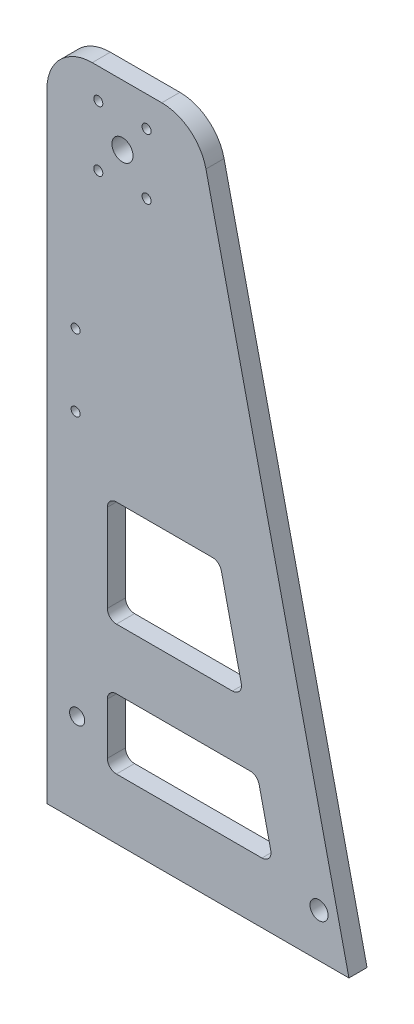
SolidWorks part; units mm, degrees
material "Policarbonato"
ref_plane "Plano frontal" through (0, 0, 0) normal (0, 0, 1) x (1, 0, 0)
ref_plane "Plano superior" through (0, 0, 0) normal (0, 1, 0) x (1, 0, 0)
ref_plane "Plano direito" through (0, 0, 0) normal (1, 0, 0) x (0, 0, -1)
sketch "Esboço1" plane through (0, 0, 0) normal (0, 0, 1) x (1, 0, 0)
  line L0 (0, 0) -> (0, 220)
  line L2 (100, 0) -> (0, 0)
  line L3 (0, 220) -> (50, 220)
  line L4 (50, 220) -> (100, 0)
  line L5 (10, 103) -> (10, 15) construction
  line L6 (25, 220) -> (25, 180) construction
  line L7 (10, 15) -> (75.8194, 15) construction
  line L8 (75.8194, 15) -> (55.8194, 103) construction
  line L9 (55.8194, 103) -> (10, 103) construction
  line L10 (20, 95) -> (20, 66)
  line L11 (23, 63) -> (61.4135, 63)
  line L12 (64.3389, 66.6649) -> (57.748, 95.6649)
  line L13 (54.8226, 98) -> (23, 98)
  line L14 (20, 40) -> (20, 23)
  line L15 (23, 20) -> (71.1862, 20)
  line L16 (74.1116, 23.6649) -> (70.248, 40.6649)
  line L17 (23, 43) -> (67.3226, 43)
  line L18 (17, 200) -> (33, 200) construction
  line L19 (17, 210) -> (33, 210) construction
  line L20 (17, 210) -> (17, 190) construction
  line L21 (17, 190) -> (33, 190) construction
  line L22 (33, 210) -> (33, 190) construction
  line L23 (17, 210) -> (33, 190) construction
  line L24 (17, 190) -> (33, 210) construction
  arc A8 (70.248, 40.6649) -> (67.3226, 43) centre (67.3226, 40) ccw
  arc A9 (71.1862, 20) -> (74.1116, 23.6649) centre (71.1862, 23) ccw
  arc A10 (20, 23) -> (23, 20) centre (23, 23) ccw
  arc A11 (20, 40) -> (23, 43) centre (23, 40) cw
  arc A12 (57.748, 95.6649) -> (54.8226, 98) centre (54.8226, 95) ccw
  arc A13 (61.4135, 63) -> (64.3389, 66.6649) centre (61.4135, 66) ccw
  arc A14 (20, 66) -> (23, 63) centre (23, 66) ccw
  arc A15 (20, 95) -> (23, 98) centre (23, 95) cw
  circle A16 centre (17, 210) radius 1.5
  circle A17 centre (33, 210) radius 1.5
  circle A18 centre (33, 190) radius 1.5
  circle A19 centre (17, 190) radius 1.5
  circle A20 centre (25, 200) radius 3.5
  circle A21 centre (10, 30) radius 2.5
  point P8 (25, 200)
  point P49 (20, 63)
  dimension "D3" = 20
  dimension "D4" = 16
  dimension "D6" = 3
  dimension "D7" = 7
  dimension "D21" = 3
  dimension "D20" = 10
  dimension "D22" = 5
  dimension "D1" = 220
  dimension "D2" = 100
  dimension "D5" = 50
  dimension "D9" = 20
  dimension "D10" = 20
  dimension "D11" = 10
  dimension "D12" = 20
  dimension "D13" = 15
  dimension "D14" = 20
  dimension "D15" = 10
  dimension "D16" = 29
  dimension "D17" = 17
  dimension "D18" = 10
  dimension "D19" = 30
  dimension "D8" = 20
extrude "Ressalto-extrusão2" add sketch "Esboço1" along normal blind 6
fillet "Filete1" radius 15 2 edges at (0, 220, 3) (50, 220, 3)
sketch "Esboço2" plane through (0, 0, 0) normal (0, 0, -1) x (-1, 0, 0)
  circle A0 centre (-90.0963, 14.5) radius 3
extrude "Corte-extrusão1" cut sketch "Esboço2" against normal blind 10
sketch "Esboço3" plane through (0, 0, 0) normal (0, 0, -1) x (-1, 0, 0)
  ellipse E2 centre (-9.5, 117.2025) end of major axis (-8, 117.2025) minor radius 1.4266
  ellipse E3 centre (-9.5, 140.9789) end of major axis (-8, 140.9789) minor radius 1.4266
extrude "Corte-extrusão2" cut sketch "Esboço3" against normal through all
